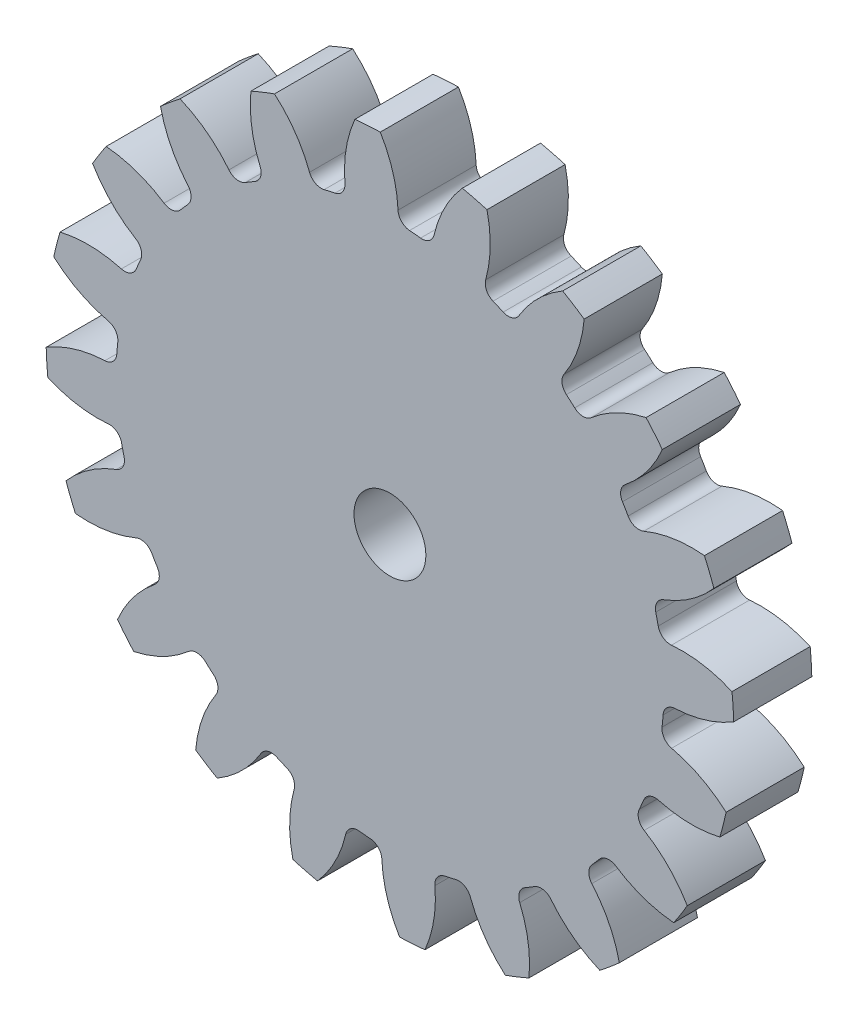
SolidWorks part; units mm, degrees
ref_plane "Front" through (0, 0, 0) normal (0, 0, 1) x (1, 0, 0)
ref_plane "Top" through (0, 0, 0) normal (0, 1, 0) x (1, 0, 0)
ref_plane "Right" through (0, 0, 0) normal (1, 0, 0) x (0, 0, -1)
sketch "Sketch3" plane through (0, 0, 0) normal (0, 0, 1) x (1, 0, 0)
  circle A0 centre (0, 0) radius 13.97
  dimension "od" = 27.94
extrude "gearBody" add sketch "Sketch3" along normal blind 3.175
sketch "Sketch2" plane through (0, 0, 0) normal (0, 0, 1) x (1, 0, 0)
  line L0 (0, 0) -> (11.3595, 4.7053) construction
  line L1 (14.9188, -4.6757) -> (0, 0) construction
  line L2 (0, 0) -> (36.3143, 0) construction
  line L3 (12.6991, -0.1527) -> (12.5125, -2.1745) construction
  line L5 (12.6058, -1.1636) -> (0, 0) construction
  line L7 (0, 0) -> (12.2955, 0) construction
  arc A0 (12.293, -0.2468) -> (12.1305, -2.0077) centre (0, 0) ccw construction
  arc A1 (13.9645, 0.3916) -> (13.6569, -2.9412) centre (0, 0) ccw construction
  arc A2 (12.6991, -0.1527) -> (12.5125, -2.1745) centre (0, 0) ccw construction
  arc A3 (11.0551, -1.2468) -> (11.0965, -0.7979) centre (0, 0) ccw
  arc A4 (14.9188, -4.6757) -> (11.4433, -1.7959) centre (10.3063, -6.7052) ccw
  arc A5 (14.9188, -4.6757) -> (15.5226, 1.8658) centre (0, 0) ccw
  arc A6 (15.5226, 1.8658) -> (11.5787, -0.3292) centre (11.3595, 4.7053) cw
  arc A7 (11.0965, -0.7979) -> (11.5787, -0.3292) centre (11.6007, -0.8342) cw
  arc A8 (11.4433, -1.7959) -> (11.0551, -1.2468) centre (11.5574, -1.3035) cw
  point P6 (15.5226, 1.8658)
  point P22 (14.9188, -4.6757)
  dimension "baseDia" = 24.591
  dimension "od" = 27.94
  dimension "pd" = 25.4
  dimension "rd" = 22.2504
  dimension "rFillet" = 0.5055
  dimension "pointX" = 15.5226
  dimension "pointY" = 1.8658
  dimension "CTT" = 2.0218
  dimension "flankCenterAngle" = 22.5
extrude "toothCut" cut sketch "Sketch2" along normal through all
pattern_circular "CirPattern1" count 20 over 360 about axis through (0, 0, 3.175) along (0, 0, -1) of "toothCut"
ref_axis "toothSpace" through (0, 0, 0) along (0.9958, -0.0919, 0)
ref_axis "Axis2" through (13.5387, -3.4444, 0) along (-0.9691, 0.2466, 0)
sketch "hub1Dia" plane through (0, 0, 0) normal (0, 0, -1) x (-1, 0, 0)
  circle A0 centre (0, 0) radius 12.7
  dimension "hub1Dia" = 25.4
sketch "hub2Dia" plane through (0, 0, 3.175) normal (0, 0, 1) x (1, 0, 0)
  circle A0 centre (0, 0) radius 12.7
  dimension "hub2dia" = 25.4
sketch "boreDia" plane through (0, 0, 0) normal (0, 0, 1) x (1, 0, 0)
  circle A0 centre (0, 0) radius 1.4605
  dimension "boreDia" = 2.921
extrude "bore" cut sketch "boreDia" against normal mid plane 25400
sketch "kwy1sketch" plane through (0, 0, 0) normal (0, 0, 1) x (1, 0, 0)
  line L0 (-5.2837, 1.0533) -> (0, 0) construction
  line L1 (28.825, 7.2038) -> (23.8594, -17.7061)
  line L2 (23.8594, -17.7061) -> (-7.278, -11.4991)
  line L3 (28.825, 7.2038) -> (-2.3123, 13.4108)
  line L4 (-7.278, -11.4991) -> (0, 0)
  line L5 (0, 0) -> (-2.3123, 13.4108)
  line L6 (0, 0) -> (11.0781, -1.0226) construction
  line L7 (26.3422, -5.2512) -> (0, 0) construction
  arc A7 (11.0551, -1.2468) -> (11.0965, -0.7979) centre (0, 0) ccw construction
  point P9 (26.3422, -5.2512)
  point P13 (-0.8814, 0.1757)
  dimension "kwy1width" = 25.4
  dimension "kwy1depth" = 26.8605
  dimension "kwy1angle" = 6
  dimension "kwy1Depth2" = 31.75
sketch "kwy2sketch" plane through (0, 0, 0) normal (0, 0, 1) x (1, 0, 0)
  line L0 (11.0781, -1.0226) -> (0, 0) construction
  line L1 (0, 0) -> (-3.0965, -2.0671) construction
  line L2 (15.2885, 25.4762) -> (29.3912, 4.351)
  line L3 (29.3912, 4.351) -> (2.9848, -13.2774)
  line L4 (15.2885, 25.4762) -> (-11.118, 7.8478)
  line L5 (2.9848, -13.2774) -> (0, 0)
  line L6 (0, 0) -> (-11.118, 7.8478)
  arc A2 (11.0551, -1.2468) -> (11.0965, -0.7979) centre (0, 0) ccw construction
  point P10 (22.3399, 14.9136)
  dimension "kwy2angle" = 39
  dimension "kwy2Width" = 25.4
  dimension "kwy2depth" = 26.8605
  dimension "kwy2Depth2" = 31.75
sketch "kwy3sketch" plane through (0, 0, 0) normal (0, 0, 1) x (1, 0, 0)
  line L0 (11.0781, -1.0226) -> (0, 0) construction
  line L1 (0, 0) -> (-0.5266, -2.6415) construction
  line L2 (-7.2038, 28.825) -> (17.7061, 23.8594)
  line L3 (17.7061, 23.8594) -> (11.4991, -7.278)
  line L4 (-7.2038, 28.825) -> (-13.4108, -2.3123)
  line L5 (11.4991, -7.278) -> (0, 0)
  line L6 (-13.4108, -2.3123) -> (0, 0)
  point P10 (5.2512, 26.3422)
  dimension "kwy3angle" = 84
  dimension "kwy3depth" = 26.8605
  dimension "kwy3width" = 25.4
  dimension "kwy3Depth2" = 31.75
sketch "kwy4sketch" plane through (0, 0, 0) normal (0, 0, 1) x (1, 0, 0)
  line L0 (11.0781, -1.0226) -> (0, 0) construction
  line L1 (0, 0) -> (1.1693, -1.7516) construction
  line L2 (-4.351, 29.3912) -> (-25.4762, 15.2885)
  line L3 (-25.4762, 15.2885) -> (-7.8478, -11.118)
  line L4 (-7.8478, -11.118) -> (0, 0)
  line L5 (13.2774, 2.9848) -> (0, 0)
  line L6 (-4.351, 29.3912) -> (13.2774, 2.9848)
  point P15 (-14.9136, 22.3399)
  dimension "kwy4angle" = 129
  dimension "kwy4depth" = 26.8605
  dimension "kwy4width" = 25.4
  dimension "kwy4Depth2" = 31.75
sketch "kwy5sketch" plane through (0, 0, 0) normal (0, 0, 1) x (1, 0, 0)
  line L0 (11.0781, -1.0226) -> (0, 0) construction
  line L1 (0, 0) -> (1.7738, -0.3536) construction
  line L2 (-23.8594, 17.7061) -> (-28.825, -7.2038)
  line L3 (-28.825, -7.2038) -> (2.3123, -13.4108)
  line L4 (-23.8594, 17.7061) -> (7.278, 11.4991)
  line L5 (2.3123, -13.4108) -> (0, 0)
  line L6 (7.278, 11.4991) -> (0, 0)
  point P10 (-26.3422, 5.2512)
  dimension "kwy5width" = 25.4
  dimension "kwy5depth" = 26.8605
  dimension "kwy5angle" = 174
  dimension "kwy5Depth2" = 31.75
sketch "kwy6sketch" plane through (0, 0, 0) normal (0, 0, 1) x (1, 0, 0)
  line L0 (11.0781, -1.0226) -> (0, 0) construction
  line L1 (0, 0) -> (1.5031, 1.0035) construction
  line L2 (-29.3912, -4.351) -> (-15.2885, -25.4762)
  line L3 (-15.2885, -25.4762) -> (11.118, -7.8478)
  line L4 (-29.3912, -4.351) -> (-2.9848, 13.2774)
  line L5 (11.118, -7.8478) -> (0, 0)
  line L6 (-2.9848, 13.2774) -> (0, 0)
  point P10 (-22.3399, -14.9136)
  dimension "kwy6angle" = 219
  dimension "kwy6width" = 25.4
  dimension "kwy6depth" = 26.8605
  dimension "kwy6Depth2" = 31.75
sketch "kwy7sketch" plane through (0, 0, 0) normal (0, 0, 1) x (1, 0, 0)
  line L0 (11.0781, -1.0226) -> (0, 0) construction
  line L1 (0, 0) -> (0.3958, 1.9857) construction
  line L2 (-17.7061, -23.8594) -> (7.2038, -28.825)
  line L3 (-17.7061, -23.8594) -> (-11.4991, 7.278)
  line L4 (7.2038, -28.825) -> (13.4108, 2.3123)
  line L5 (-11.4991, 7.278) -> (0, 0)
  line L6 (13.4108, 2.3123) -> (0, 0)
  point P10 (-5.2512, -26.3422)
  dimension "kwy7angle" = 84
  dimension "kwy7width" = 25.4
  dimension "kwy7depth" = 26.8605
  dimension "kwy7angle1" = 264
  dimension "kwy7Depth2" = 31.75
sketch "kwy8sketch" plane through (0, 0, 0) normal (0, 0, 1) x (1, 0, 0)
  line L0 (11.0781, -1.0226) -> (0, 0) construction
  line L1 (0, 0) -> (-0.9988, 1.4961) construction
  line L2 (4.351, -29.3912) -> (25.4762, -15.2885)
  line L3 (25.4762, -15.2885) -> (7.8478, 11.118)
  line L4 (4.351, -29.3912) -> (-13.2774, -2.9848)
  line L5 (7.8478, 11.118) -> (0, 0)
  line L6 (-13.2774, -2.9848) -> (0, 0)
  point P10 (14.9136, -22.3399)
  dimension "kwy8angle" = 309
  dimension "kwy8width" = 25.4
  dimension "kwy8depth" = 26.8605
  dimension "kwy8Depth2" = 31.75
sketch "centerLine" plane through (0, 0, 0) normal (0, 1, 0) x (1, 0, 0)
  line L0 (0, 36.4807) -> (0, -59.6309) construction
ref_plane "CB1plane" through (0, 0, 0) normal (0, 0, -1) x (-1, 0, 0)
sketch "CB1diameter" plane through (0, 0, 0) normal (0, 0, -1) x (-1, 0, 0)
  circle A0 centre (0, 0) radius 12.7
  dimension "CB1diameter" = 25.4
ref_plane "CB2plane" through (0, 0, 3.175) normal (0, 0, 1) x (1, 0, 0)
sketch "CB2diameter" plane through (0, 0, 3.175) normal (0, 0, 1) x (1, 0, 0)
  circle A0 centre (0, 0) radius 12.7
  dimension "CB2diameter" = 25.4
ref_axis "Axis1" through (0, 0, 50) along (0, 0, -1)
sketch3d "3DSketch1" plane through (0, 0, 0) normal (0, 0, 1) x (1, 0, 0)
